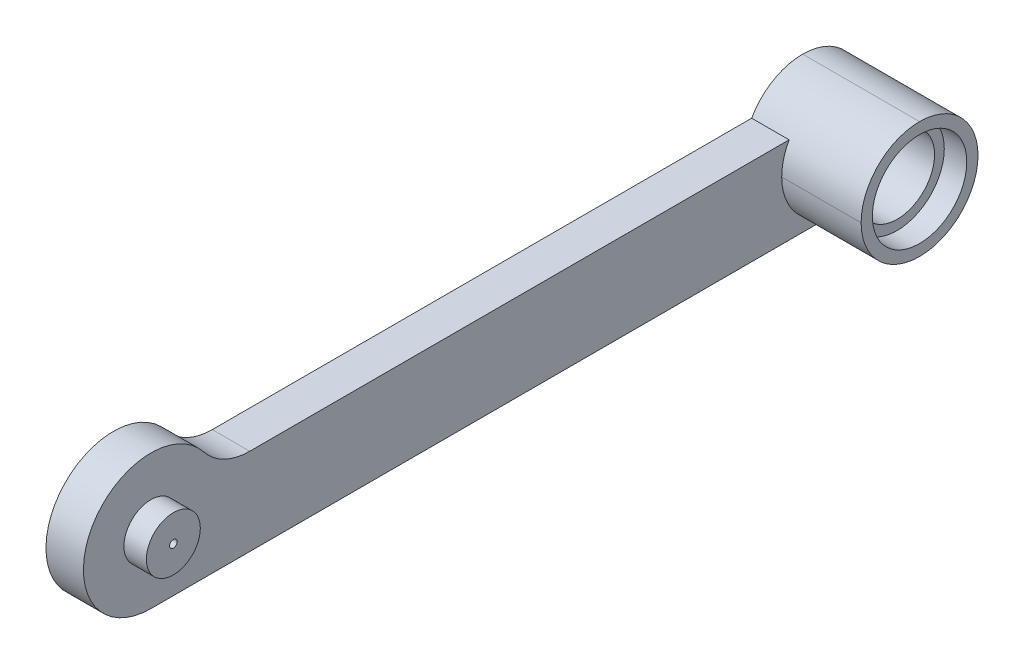
SolidWorks part; units mm, degrees
ref_plane "前视基准面" through (0, 0, 0) normal (0, 0, 1) x (1, 0, 0)
ref_plane "上视基准面" through (0, 0, 0) normal (0, 1, 0) x (1, 0, 0)
ref_plane "右视基准面" through (0, 0, 0) normal (1, 0, 0) x (0, 0, -1)
other "Configuration Table"
sketch "草图1" plane through (0, 0, 0) normal (1, 0, 0) x (0, 0, -1)
  line L0 (46, 3.3) -> (46, -4.5) construction
  line L1 (0, -4.5) -> (49.9, -4.5)
  line L2 (0, -4.5) -> (0, 3.3)
  line L3 (0, 3.3) -> (49.9, 3.3)
  line L4 (49.9, -4.5) -> (49.9, 3.3)
  line L6 (42.1, -4.5) -> (49.9, -4.5)
  line L7 (42.1, -4.5) -> (42.1, 3.3)
  line L8 (42.1, 3.3) -> (49.9, 3.3)
  line L9 (49.9, -4.5) -> (49.9, 3.3)
  line L10 (42.1, -4.5) -> (49.9, 3.3) construction
  line L11 (42.1, 3.3) -> (49.9, -4.5) construction
  circle A4 centre (0, 0) radius 1.8
  circle A5 centre (0, 0) radius 4.5
  circle A6 centre (46, -0.6) radius 2.5
  circle A7 centre (46, -0.6) radius 3.15
  circle A8 centre (0, 0) radius 0.25
  point P9 (46, -0.6)
  dimension "D1" = 3.6
  dimension "D4" = 46
  dimension "D5" = 3.9
  dimension "D2" = 9
  dimension "D6" = 5
  dimension "D7" = 6.3
  dimension "D8" = 0.5
  dimension "D3" = 7.8
extrude "凸台-拉伸1" add sketch "草图1" along normal blind 2.5 contours A5 | L3 L4 L1 L2
extrude "凸台-拉伸3" add sketch "草图1<6>" along normal blind 1.5 from surface contours L2 A4 | L2 A4 region at (0, 0, 0.7769) region at (0, 0, -0.7769) starting at face at (2.5, -0.0392, -24.2851)
sketch "草图1<6>" plane through (0, 0, 0) normal (1, 0, 0) x (0, 0, -1) same geometry as "草图1"
extrude "凸台-拉伸2" add sketch "草图1<5>" along normal blind 7.8 contours A6 | A7 A6 | L7 L1 L4 L3 A7 region at (0, -0.6, -42.2103) region at (0, -0.6, -46) region at (0, -0.6, -42.9391)
sketch "草图1<5>" plane through (0, 0, 0) normal (1, 0, 0) x (0, 0, -1) same geometry as "草图1"
extrude "切除-拉伸1" cut sketch "草图1<7>" along normal through all contours A6 region at (0, -0.6, -46)
sketch "草图1<7>" plane through (0, 0, 0) normal (1, 0, 0) x (0, 0, -1) same geometry as "草图1"
extrude "切除-拉伸2" cut sketch "草图1<8>" along normal blind 1.5 contours A7 A6 region at (0, -0.6, -42.9391)
sketch "草图1<8>" plane through (0, 0, 0) normal (1, 0, 0) x (0, 0, -1) same geometry as "草图1"
extrude "切除-拉伸3" cut sketch "草图1<9>" against normal blind 1.5 from surface contours A7 A6 region at (0, -0.6, -42.9391) starting at face at (7.8, -0.6, -48.5)
sketch "草图1<9>" plane through (0, 0, 0) normal (1, 0, 0) x (0, 0, -1) same geometry as "草图1"
sketch "草图2" plane through (0, 0, 0) normal (-1, 0, 0) x (0, 0, 1)
  line L0 (-3.0594, 3.3) -> (-49.9, 3.3) construction
  line L1 (-42.1, 3.3) -> (-4.5, 3.3)
  line L2 (-42.1, 3.3) -> (-42.1, 1.3)
  line L3 (-42.1, 1.3) -> (-4.5, 1.3)
  line L4 (-4.5, 3.3) -> (-4.5, 1.3)
  line L5 (-42.1, 3.3) -> (-42.1, -4.5) construction
  line L6 (-4.5, 3.3) -> (-3.0594, 3.3)
  line L8 (-4.5, 1.3) -> (-4.3081, 1.3)
  line L9 (-4.5, 1.3) -> (-4.5, 3.3)
  line L10 (-4.5, 3.3) -> (-4.3081, 3.3)
  line L11 (-4.3081, 1.3) -> (-4.3081, 3.3)
  arc A1 (0, -4.5) -> (-3.0594, 3.3) centre (0, 0) ccw construction
  circle A2 centre (0, 0) radius 4.5
  line M7 (-3.0594, 3.3) -> (-49.9, 3.3)
  dimension "D1" = 2
extrude "切除-拉伸4" cut sketch "草图2" against normal through all contours A2 L11 M7 | L8 L11 L6 L4 | L4 L2 L3 M7 region at (0, 2.3, -23.3) region at (0, 2.3, -4.4041) region at (0, 2.7076, -3.9302)
fillet "圆角1" radius 3.9 5 edges at (3.9, -4.5, -49.9) (3.9, 3.3, -49.9) (5.15, -4.5, -42.1) (3.9, 3.3, -42.1) (1.25, 1.3, -4.3081)
ref_plane "基准面1" through (-1, 0, 0) normal (-1, 0, 0) x (0, 0, 1)
mirror "镜向2" about plane through (-1, 0, 0) normal (-1, 0, 0) of bodies 118 114
sketch "草图3" plane through (-4.5, 0, 0) normal (0, -1, 0) x (0, 0, 1)
  line L1 (-55.5542, 7.4344) -> (21.7164, 7.4344)
  line L2 (-55.5542, 7.4344) -> (-55.5542, -3.5409)
  line L3 (-55.5542, -3.5409) -> (21.7164, -3.5409)
  line L4 (21.7164, 7.4344) -> (21.7164, -3.5409)
extrude "切除-拉伸5" cut sketch "草图3" against normal through all both and the other way through all
